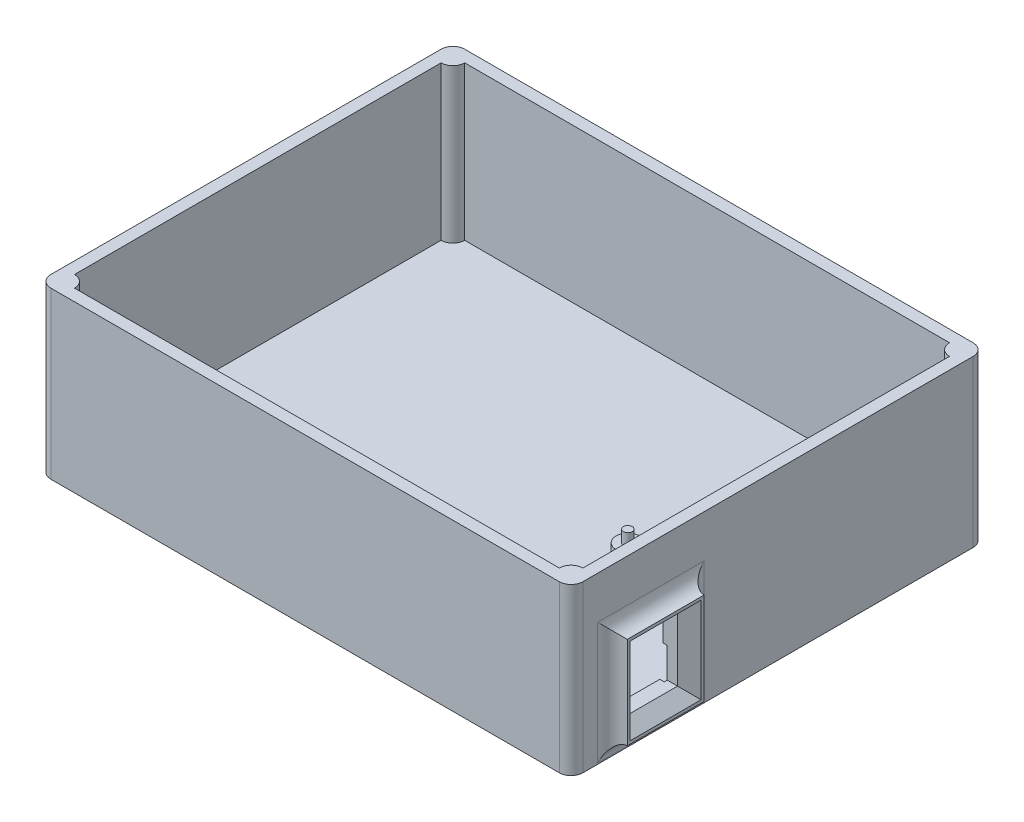
SolidWorks part; units mm, degrees
ref_plane "Front Plane" through (0, 0, 0) normal (0, 0, 1) x (1, 0, 0)
ref_plane "Top Plane" through (0, 0, 0) normal (0, 1, 0) x (1, 0, 0)
ref_plane "Right Plane" through (0, 0, 0) normal (1, 0, 0) x (0, 0, -1)
sketch "Sketch1" plane through (0, 0, 0) normal (0, 1, 0) x (1, 0, 0)
  line L1 (57.15, 44.45) -> (-57.15, 44.45)
  line L2 (57.15, 44.45) -> (57.15, -44.45)
  line L3 (57.15, -44.45) -> (-57.15, -44.45)
  line L4 (-57.15, 44.45) -> (-57.15, -44.45)
  line L5 (57.15, 44.45) -> (-57.15, -44.45) construction
  line L6 (57.15, -44.45) -> (-57.15, 44.45) construction
  point P0 (0, 0)
  dimension "D1" = 88.9
  dimension "D2" = 114.3
extrude "Boss-Extrude1" add sketch "Sketch1" along normal blind 35.56
shell "Shell1" thickness 2.54 removed face at (0, 35.56, 0)
fillet "Fillet1" radius 2.54 8 edges at (54.61, 19.05, -41.91) (-54.61, 19.05, -41.91) (-54.61, 19.05, 41.91) (54.61, 19.05, 41.91) (-57.15, 17.78, 44.45) (-57.15, 17.78, -44.45) (57.15, 17.78, 44.45) (57.15, 17.78, -44.45)
sketch "Sketch2" plane through (0, 35.56, 0) normal (0, 1, 0) x (1, 0, 0)
  circle A0 centre (-54.61, 41.91) radius 2.54
  circle A1 centre (54.61, 41.91) radius 2.54
  circle A2 centre (54.61, -41.91) radius 2.54
  circle A3 centre (-54.61, -41.91) radius 2.54
  dimension "D1" = 5.08
extrude "Boss-Extrude2" add sketch "Sketch2" against normal up to surface (33.02 mm away) up to face at (0, 2.54, 0)
sketch "Sketch4" plane through (54.61, 0, 0) normal (-1, 0, 0) x (0, 0, 1)
  line L0 (39.37, 2.54) -> (-39.37, 2.54) construction
  line L1 (8.89, 2.54) -> (22.86, 2.54)
  line L2 (8.89, 2.54) -> (8.89, 13.081)
  line L3 (8.89, 13.081) -> (22.86, 13.081)
  line L4 (22.86, 2.54) -> (22.86, 13.081)
  line L5 (22.86, 18.161) -> (22.86, 7.239) construction
  line L6 (22.86, 18.161) -> (31.75, 18.161) construction
  dimension "D1" = 0
  dimension "D2" = 5.08
  dimension "D3" = 13.97
extrude "Cut-Extrude2" cut sketch "Sketch4" against normal blind 0.9525
sketch "Sketch5" plane through (0, 2.54, 0) normal (0, 1, 0) x (1, 0, 0)
  circle A0 centre (24.892, 0) radius 2.54
  circle A1 centre (50.292, 0) radius 2.54
  circle A2 centre (24.892, -35.56) radius 2.54
  circle A3 centre (50.292, -35.56) radius 2.54
  dimension "D1" = 5.08
extrude "Boss-Extrude3" add sketch "Sketch5" along normal blind 3.175
sketch "Sketch6" plane through (0, 5.715, 0) normal (0, 1, 0) x (1, 0, 0)
  circle A0 centre (24.892, 0) radius 0.9525
  circle A1 centre (50.292, 0) radius 0.9525
  circle A2 centre (50.292, -35.56) radius 0.9525
  circle A3 centre (24.892, -35.56) radius 0.9525
  dimension "D1" = 1.905
extrude "Boss-Extrude4" add sketch "Sketch6" along normal blind 2.54
sketch "Sketch7" plane through (57.15, 0, 0) normal (1, 0, 0) x (0, 0, -1)
  line L0 (-31.75, 7.239) -> (-22.86, 7.239) construction
  line L1 (-32.385, 20.066) -> (-22.225, 20.066)
  line L2 (-32.385, 20.066) -> (-32.385, 6.604)
  line L3 (-32.385, 6.604) -> (-22.225, 6.604)
  line L4 (-22.225, 20.066) -> (-22.225, 6.604)
  line L5 (-32.385, 20.066) -> (-22.225, 6.604) construction
  line L6 (-32.385, 6.604) -> (-22.225, 20.066) construction
  line L7 (-22.86, 18.161) -> (-22.86, 7.239) construction
  line L8 (-31.75, 18.161) -> (-31.75, 7.239) construction
  line L9 (-31.75, 18.161) -> (-22.86, 18.161) construction
  point P0 (-27.305, 13.335)
  dimension "D1" = 0.635
  dimension "D2" = 0.635
  dimension "D3" = 0.635
  dimension "D4" = 1.905
extrude "Cut-Extrude3" cut sketch "Sketch7" against normal up to next
sketch "Sketch8" plane through (57.15, 0, 0) normal (1, 0, 0) x (0, 0, -1)
  line L0 (-35.56, 23.241) -> (-19.05, 23.241)
  line L1 (-32.385, 6.604) -> (-22.225, 6.604)
  line L2 (-32.385, 6.604) -> (-32.385, 20.066)
  line L3 (-32.385, 20.066) -> (-22.225, 20.066)
  line L4 (-22.225, 6.604) -> (-22.225, 20.066)
  line L5 (-19.05, 3.429) -> (-19.05, 23.241)
  line L6 (-35.56, 3.429) -> (-19.05, 3.429)
  line L7 (-35.56, 3.429) -> (-35.56, 23.241)
  dimension "D1" = 3.175
extrude "Boss-Extrude5" add sketch "Sketch8" along normal blind 3.175
chamfer "Chamfer1" distance 2.54 angle 45 4 edges at (60.325, 6.604, 27.305) (60.325, 13.335, 22.225) (60.325, 20.066, 27.305) (60.325, 13.335, 32.385)
fillet "Fillet2" radius 3.175 4 edges at (57.15, 3.429, 27.305) (57.15, 13.335, 19.05) (57.15, 23.241, 27.305) (57.15, 13.335, 35.56)
